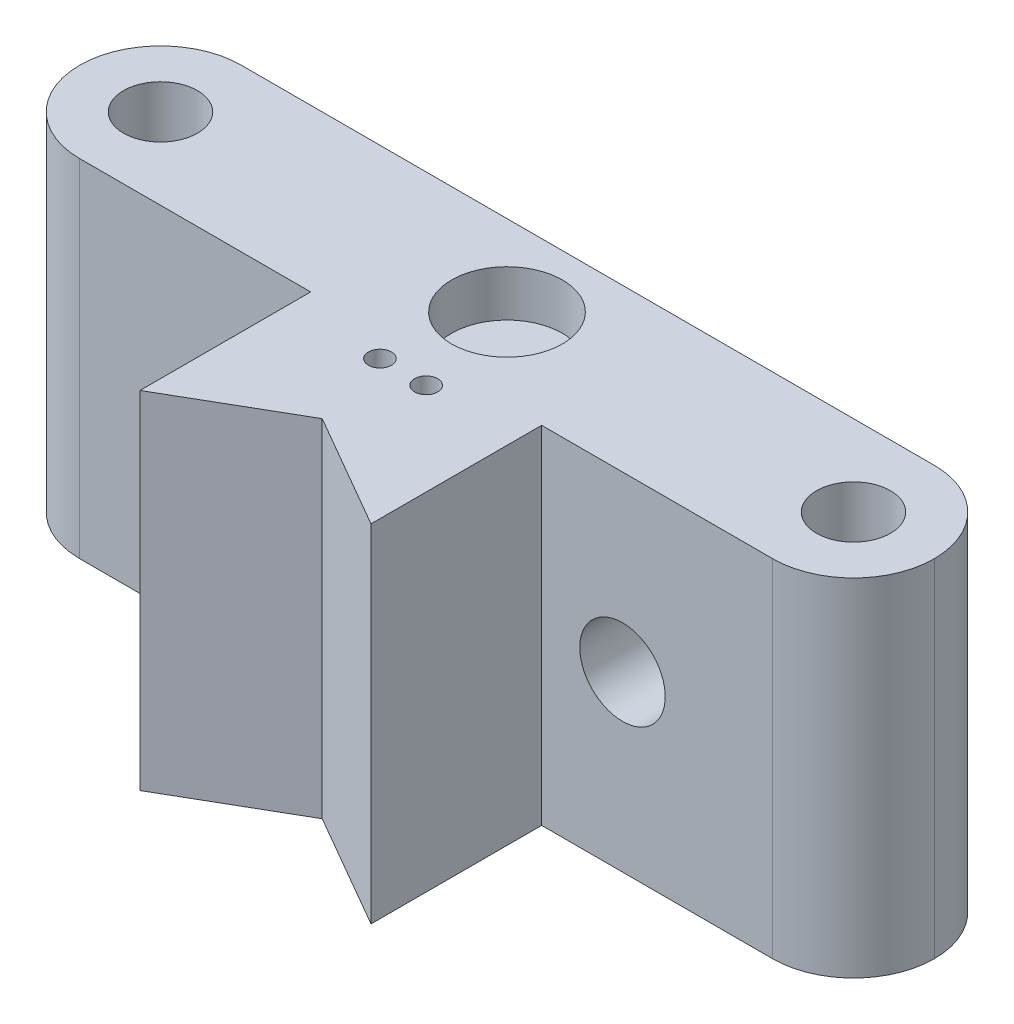
SolidWorks part; units mm, degrees
ref_plane "Ebene vorne" through (0, 0, 0) normal (0, 0, 1) x (1, 0, 0)
ref_plane "Ebene oben" through (0, 0, 0) normal (0, 1, 0) x (1, 0, 0)
ref_plane "Ebene rechts" through (0, 0, 0) normal (1, 0, 0) x (0, 0, -1)
sketch "Skizze1" plane through (0, 0, 0) normal (0, 1, 0) x (1, 0, 0)
  line L0 (-18.5, 0) -> (18.5, 0) construction
  line L1 (-18.5, 3.5) -> (18.5, 3.5)
  line L2 (-18.5, 3.5) -> (-18.5, -3.5)
  line L3 (-18.5, -3.5) -> (18.5, -3.5)
  line L4 (18.5, 3.5) -> (18.5, -3.5)
  line L5 (-5, -10.8868) -> (0, -8)
  line L10 (-5, -3.5) -> (5, -3.5)
  line L11 (-5, -3.5) -> (-5, -10.8868)
  line L12 (-5, -10.8868) -> (5, -10.8868)
  line L13 (5, -3.5) -> (5, -10.8868)
  line L14 (0, -8) -> (5, -10.8868)
  line L15 (-1, -4.5) -> (1, -4.5) construction
  circle A0 centre (-15, 0) radius 1.6
  circle A1 centre (15, 0) radius 1.6
  circle A2 centre (-1, -4.5) radius 0.5
  circle A3 centre (1, -4.5) radius 0.5
  circle A4 centre (0, 0) radius 2.4
  point P4 (-18.5, 0)
  point P6 (0, -3.5)
  point P22 (0, -10.8868)
  point P23 (0, -4.5)
  dimension "D3" = 3.2
  dimension "D4" = 3.2
  dimension "D12" = 1
  dimension "D13" = 1
  dimension "D14" = 4.8
  dimension "D1" = 30
  dimension "D2" = 7
  dimension "D5" = 15
  dimension "D6" = 3.5
  dimension "D7" = 4.5
  dimension "D8" = 120
  dimension "D9" = 10
  dimension "D10" = 1
  dimension "D11" = 2
extrude "Aufsatz-Linear austragen1" add sketch "Skizze1" along normal mid plane 15 contours L4 L1 L2 L3 A4 A1 A0 | A4 | L5 L14 L13 L3 L11 A3 A2 region at (0, 0, -3.1234) region at (0, 0, 6.5852) region at (0, 0, 0)
fillet "Verrundung1" radius 3.5 4 edges at (-18.5, 0, 3.5) (-18.5, 0, -3.5) (18.5, 0, -3.5) (18.5, 0, 3.5)
sketch "Skizze2" plane through (0, 0, -3.5) normal (0, 0, -1) x (-1, 0, 0)
  line L0 (-8.5, 0) -> (8.5, 0) construction
  line L1 (15, -7.5) -> (15, 7.5) construction
  circle A0 centre (-8.5, 0) radius 1.85
  circle A1 centre (8.5, 0) radius 1.85
  point P4 (0, 0)
  point P8 (15, 0)
  dimension "D2" = 3.7
  dimension "D3" = 3.7
  dimension "D1" = 17
  dimension "D4" = 0
extrude "Schnitt-Linear austragen1" cut sketch "Skizze2" against normal through all
sketch "Skizze3" plane through (0, 7.5, 0) normal (0, 1, 0) x (1, 0, 0)
  circle A0 centre (0, 0) radius 2.4
  dimension "D1" = 4.8
extrude "Schnitt-Linear austragen2" cut sketch "Skizze3" against normal blind 2
